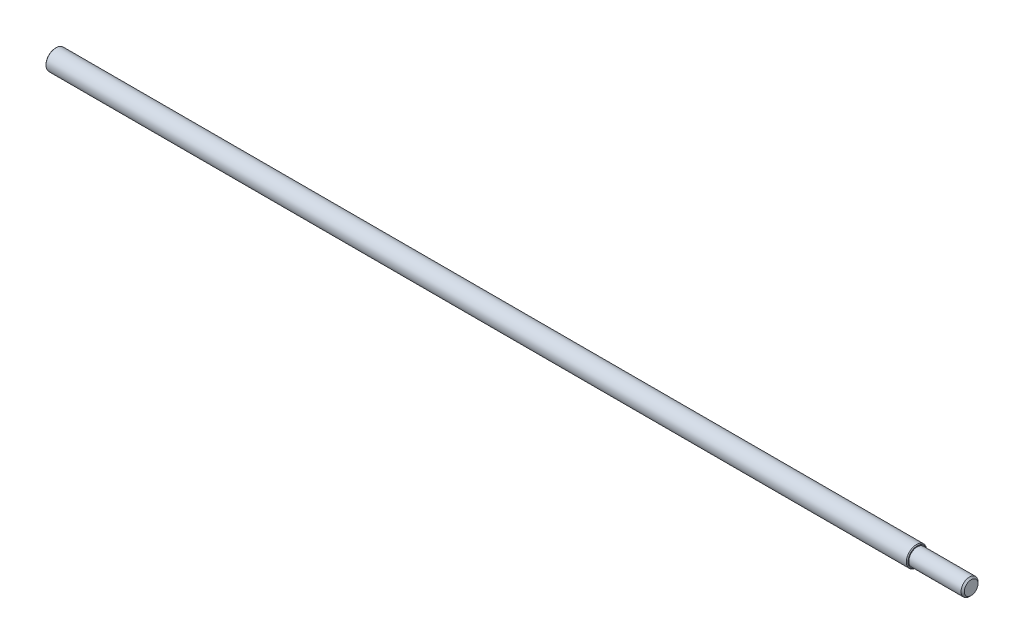
SolidWorks part; units mm, degrees
ref_plane "Front Plane" through (0, 0, 0) normal (0, 0, 1) x (1, 0, 0)
ref_plane "Top Plane" through (0, 0, 0) normal (0, 1, 0) x (1, 0, 0)
ref_plane "Right Plane" through (0, 0, 0) normal (1, 0, 0) x (0, 0, -1)
sketch "Sketch1" plane through (0, 0, 0) normal (1, 0, 0) x (0, 0, -1)
  circle A0 centre (0, 0) radius 4.7625 construction
  circle A2 centre (0, 0) radius 4.7879 construction
  dimension "Diameter" = 9.525
  dimension "Finish Thickness" = 0.0254
sketch "Sketch2" plane through (0, 0, 0) normal (0, 0, 1) x (1, 0, 0)
  line L0 (0, 0) -> (304.8, 0) construction
  line L1 (0, 0) -> (-304.8, 0) construction
  line L2 (304.8, 0) -> (304.8, 4.7625) construction
  line L3 (304.8, 0) -> (304.8, -4.7625) construction
  line L4 (304.8, 4.7625) -> (0, 4.7625) construction
  line L7 (0, 4.7625) -> (-304.8, 4.7625) construction
  line L8 (-304.8, 4.7625) -> (-304.8, 0) construction
  point P5 (-254, 0)
  point P8 (254, 0)
  dimension "Length" = 609.6
  dimension "D1" = 50.8
  dimension "D2" = 50.8
sketch "Sketch4" plane through (0, 0, 0) normal (1, 0, 0) x (0, 0, -1)
  circle A0 centre (0, 0) radius 4.7625 construction
  circle A1 centre (0, 0) radius 4.7625
extrude "Boss-Extrude1" add sketch "Sketch4" along normal up to vertex (304.8 mm away) and the other way up to vertex (304.8 mm away) up to point (304.8, 0, 0) other way up to point (-304.8, 0, 0)
chamfer "Chamfer1" distance 0.2476 angle 45 2 edges at (-304.8, 0, -4.7625) (304.8, 0, -4.7625)
sketch "Sketch5" plane through (0, 0, 0) normal (0, 0, 1) x (1, 0, 0)
  line L0 (304.8, 0) -> (127, 0)
  line L1 (304.8, -4.5149) -> (304.8, 4.5149) construction
  line L2 (127, 0) -> (127, 3.238)
  line L3 (127, 3.238) -> (126.238, 4)
  line L4 (126.238, 4) -> (101.6, 4)
  line L5 (101.6, 4) -> (101.6, 4.3815)
  line L6 (101.6, 4.3815) -> (101.219, 4.7625)
  line L7 (304.5524, 4.7625) -> (-304.5523, 4.7625) construction
  line L8 (101.219, 4.7625) -> (304.8, 4.7625)
  line L9 (304.8, 4.7625) -> (304.8, 0)
  line L10 (127, 0) -> (239.2618, 0) construction
  line L11 (-304.8, 4.5148) -> (-304.8, -4.5148) construction
  point P16 (164.8182, 4)
  point P17 (120.4321, 4.1219)
  point P18 (95.687, 4.1219)
  point P19 (0, 0)
  point P20 (106.4891, 4)
  point P21 (127, 3.5219)
  point P22 (125.7583, 4)
  point P23 (106.5164, 4.3872)
  point P24 (106.0535, 4.7625)
  dimension "D1" = 8
  dimension "D2" = 431.8
  dimension "D3" = 45
  dimension "D4" = 0.762
  dimension "D5" = 0.381
  dimension "D6" = 45
  dimension "D7" = 25.4
revolve "Cut-Revolve1" cut sketch "Sketch5" angle 360 about L10
equation "\"D1@Chamfer1\" = \"Diameter@Sketch1\" * .026"
equation "\"D2@Sketch2\" = \"D1@Sketch2\""
